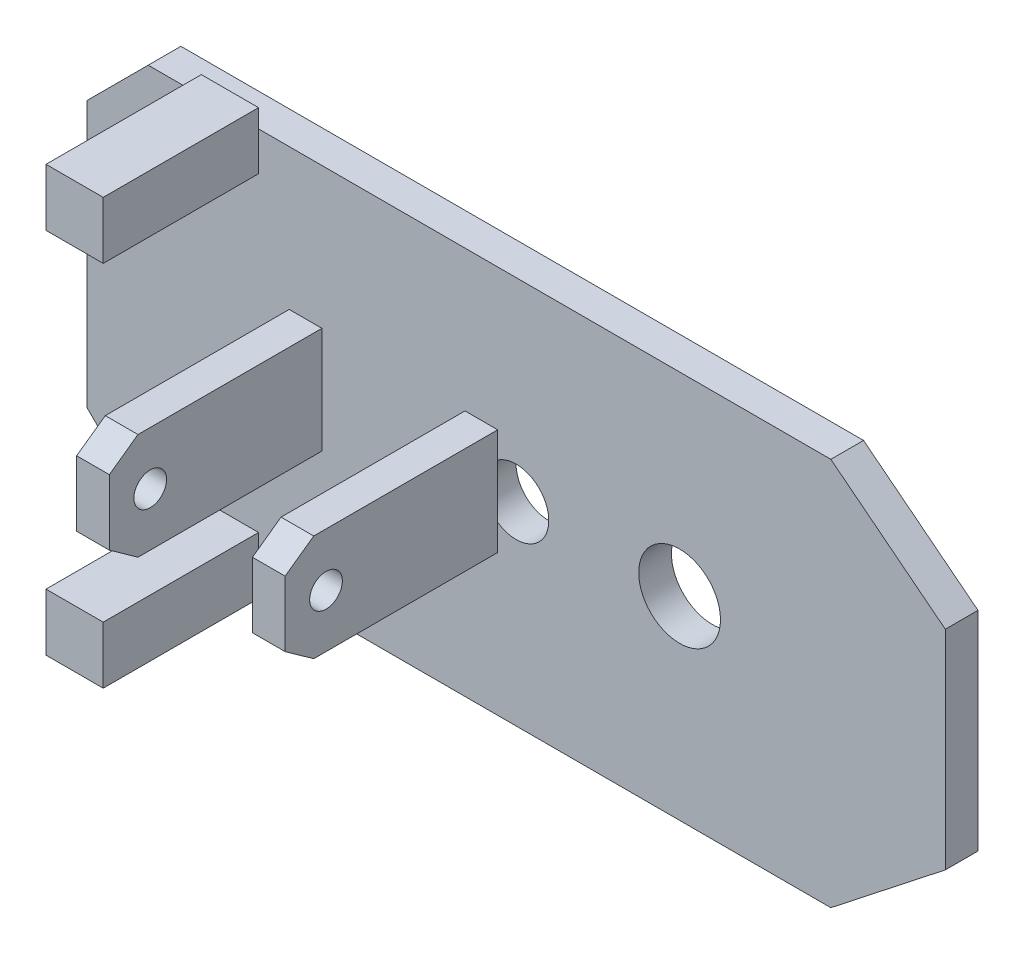
SolidWorks part; units mm, degrees
ref_plane "Front Plane" through (0, 0, 0) normal (0, 0, 1) x (1, 0, 0)
ref_plane "Top Plane" through (0, 0, 0) normal (0, 1, 0) x (1, 0, 0)
ref_plane "Right Plane" through (0, 0, 0) normal (1, 0, 0) x (0, 0, -1)
ref_plane "PL_Sole_Plate_base" through (0, 0, -50) normal (0, 0, 1) x (1, 0, 0)
sketch "SK_Sole_Plate" plane through (0, 0, -50) normal (0, 0, 1) x (1, 0, 0)
  line L0 (-60, 47.5) -> (107, 47.5)
  line L1 (107, 47.5) -> (135, 25.5)
  line L2 (135, 25.5) -> (135, -25.5)
  line L3 (135, -25.5) -> (107, -47.5)
  line L4 (107, -47.5) -> (-60, -47.5)
  line L5 (-60, -47.5) -> (-75, -32.5)
  line L6 (-75, -32.5) -> (-75, 32.5)
  line L7 (-75, 32.5) -> (-60, 47.5)
  circle A0 centre (70, 0) radius 10
  circle A1 centre (30, 0) radius 8
  dimension "D17_SK_Sole_Plate" = 20
  dimension "D19_SK_Sole_Plate" = 16
  dimension "P1" = 60
  dimension "P2" = 47.5
  dimension "P3" = 107
  dimension "P4" = 47.5
  dimension "P5" = 135
  dimension "P6" = 25.5
  dimension "P7" = 135
  dimension "P8" = 25.5
  dimension "P9" = 107
  dimension "P10" = 47.5
  dimension "P11" = 60
  dimension "P12" = 47.5
  dimension "P13" = 75
  dimension "P14" = 32.5
  dimension "P15" = 75
  dimension "P16" = 32.5
  dimension "P18" = 70
  dimension "P20" = 30
extrude "Sole_Plate" add sketch "SK_Sole_Plate" along normal blind 8
ref_plane "PL_Clevis_Front_base" through (17.5, 0, 0) normal (1, 0, 0) x (0, 0, -1)
sketch "SK_Clevis_Front" plane through (17.5, 0, 0) normal (1, 0, 0) x (0, 0, -1)
  line L0 (42, 13) -> (42, -13)
  line L1 (42, -13) -> (-3, -13)
  line L2 (-3, -13) -> (-10, -8)
  line L3 (-10, -8) -> (-10, 8)
  line L4 (-10, 8) -> (-3, 13)
  line L5 (-3, 13) -> (42, 13)
  circle A0 centre (0, 0) radius 4
  dimension "D13_SK_Clevis_Front" = 8
  dimension "P1" = 42
  dimension "P2" = 13
  dimension "P3" = 42
  dimension "P4" = 13
  dimension "P5" = 3
  dimension "P6" = 13
  dimension "P7" = 10
  dimension "P8" = 8
  dimension "P9" = 10
  dimension "P10" = 8
  dimension "P11" = 3
  dimension "P12" = 13
extrude "Clevis_Front" add sketch "SK_Clevis_Front" along normal blind 8
ref_plane "PL_Clevis_Back_base" through (-25.5, 0, 0) normal (1, 0, 0) x (0, 0, -1)
sketch "SK_Clevis_Back" plane through (-25.5, 0, 0) normal (1, 0, 0) x (0, 0, -1)
  line L0 (42, 13) -> (42, -13)
  line L1 (42, -13) -> (-3, -13)
  line L2 (-3, -13) -> (-10, -8)
  line L3 (-10, -8) -> (-10, 8)
  line L4 (-10, 8) -> (-3, 13)
  line L5 (-3, 13) -> (42, 13)
  circle A0 centre (0, 0) radius 4
  dimension "D13_SK_Clevis_Back" = 8
  dimension "P1" = 42
  dimension "P2" = 13
  dimension "P3" = 42
  dimension "P4" = 13
  dimension "P5" = 3
  dimension "P6" = 13
  dimension "P7" = 10
  dimension "P8" = 8
  dimension "P9" = 10
  dimension "P10" = 8
  dimension "P11" = 3
  dimension "P12" = 13
extrude "Clevis_Back" add sketch "SK_Clevis_Back" along normal blind 8
ref_plane "PL_Post_Lat_base" through (0, 0, -42) normal (0, 0, 1) x (1, 0, 0)
sketch "SK_Post_Lat" plane through (0, 0, -42) normal (0, 0, 1) x (1, 0, 0)
  line L0 (-47, -38) -> (-33, -38)
  line L1 (-33, -38) -> (-33, -52)
  line L2 (-33, -52) -> (-47, -52)
  line L3 (-47, -52) -> (-47, -38)
  dimension "P1" = 47
  dimension "P2" = 38
  dimension "P3" = 33
  dimension "P4" = 38
  dimension "P5" = 33
  dimension "P6" = 52
  dimension "P7" = 47
  dimension "P8" = 52
extrude "Post_Lat" add sketch "SK_Post_Lat" along normal blind 38
ref_plane "PL_Post_Med_base" through (0, 0, -42) normal (0, 0, 1) x (1, 0, 0)
sketch "SK_Post_Med" plane through (0, 0, -42) normal (0, 0, 1) x (1, 0, 0)
  line L0 (-47, 52) -> (-33, 52)
  line L1 (-33, 52) -> (-33, 38)
  line L2 (-33, 38) -> (-47, 38)
  line L3 (-47, 38) -> (-47, 52)
  dimension "P1" = 47
  dimension "P2" = 52
  dimension "P3" = 33
  dimension "P4" = 52
  dimension "P5" = 33
  dimension "P6" = 38
  dimension "P7" = 47
  dimension "P8" = 38
extrude "Post_Med" add sketch "SK_Post_Med" along normal blind 38
ref_axis "AX_Roll" through (-85.5, 0, 0) along (1, 0, 0)
sketch "SK_RodBalls" plane through (0, 0, 0) normal (0, 0, 1) x (1, 0, 0)
  point P0 (-40, -45)
  point P2 (-40, 45)
  dimension "P1" = 40
  dimension "P2" = 45
  dimension "P3" = 40
  dimension "P4" = 45
equation "\"Foot_length\" = 210"
equation "\"Foot_width\" = 95"
equation "\"Ankle_height\" = 50"
